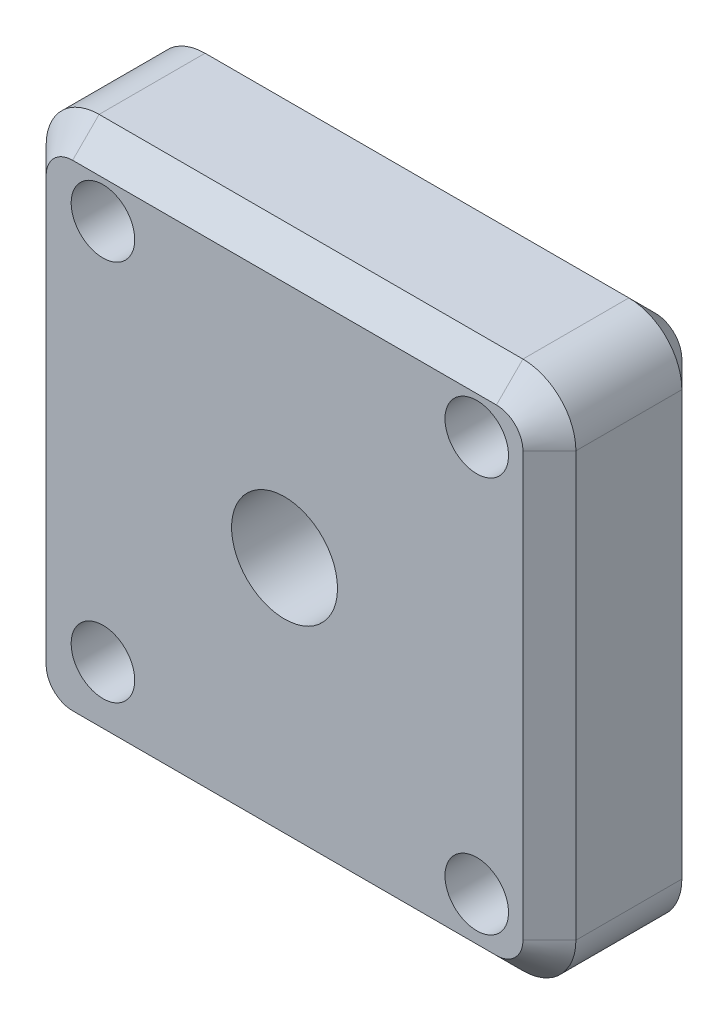
SolidWorks part; units mm, degrees
ref_plane "Front Plane" through (0, 0, 0) normal (0, 0, 1) x (1, 0, 0)
ref_plane "Top Plane" through (0, 0, 0) normal (0, 1, 0) x (1, 0, 0)
ref_plane "Right Plane" through (0, 0, 0) normal (1, 0, 0) x (0, 0, -1)
sketch "Sketch1" plane through (0, 0, 0) normal (0, 0, 1) x (1, 0, 0)
  line L5 (50, -50) -> (-50, -50)
  line L6 (50, -50) -> (50, 50)
  line L7 (50, 50) -> (-50, 50)
  line L8 (-50, -50) -> (-50, 50)
  point P0 (0, 0)
  dimension "D1" = 100
  dimension "D2" = 100
extrude "Boss-Extrude1" add sketch "Sketch1" along normal blind 30
sketch "Sketch3" plane through (0, 0, 30) normal (0, 0, 1) x (1, 0, 0)
  circle A0 centre (0, 0) radius 10
  dimension "D1" = 20
extrude "Cut-Extrude1" cut sketch "Sketch3" against normal through all and the other way blind 19 contours A0
fillet "Fillet1" radius 10 4 edges at (-50, -50, 15) (-50, 50, 15) (50, 50, 15) (50, -50, 15)
chamfer "Chamfer1" distance 5 angle 45 16 edges at (0, 50, 0) (-47.0711, 47.0711, 0) (47.0711, 47.0711, 0) (-50, 0, 0) (50, 0, 0) (-47.0711, -47.0711, 0) (47.0711, -47.0711, 0) (0, -50, 0) (50, 0, 30) (47.0711, 47.0711, 30) (47.0711, -47.0711, 30) (0, 50, 30) (0, -50, 30) (-47.0711, 47.0711, 30) (-47.0711, -47.0711, 30) (-50, 0, 30)
hole_wizard "Ø12.0mm Dowel Hole1" positions "Sketch4" profile "Sketch5" hole size "Ø12.0" standard "ISO" end condition through all
sketch "Sketch4" plane through (0, 0, 0) normal (0, 0, -1) x (-1, 0, 0)
  point P0 (-36.2836, 37.8873)
  point P2 (34.279, 37.8873)
  point P4 (34.279, -34.1454)
  point P6 (-36.2836, -36.8182)
sketch "Sketch5" plane through (36.2836, 37.8873, 0) normal (1, 0, 0) x (0, 1, 0)
  line L0 (0, 0) -> (0, 30)
  line L1 (0, 30) -> (6, 30)
  line L2 (6, 30) -> (6, 0.025)
  line L3 (6, 0.025) -> (6.025, 0)
  line L5 (6.025, 0) -> (0, 0)
  line L6 (-6, 0.025) -> (-6.025, 0) construction
  line L11 (0, -6.35) -> (0, 107.95) construction
  dimension "Thru Hole Dia." = 12
  dimension "Thru Hole Depth" = 30
  dimension "Near C'Sink Dia." = 12.05
  dimension "Near C'Sink Angle" = 90
